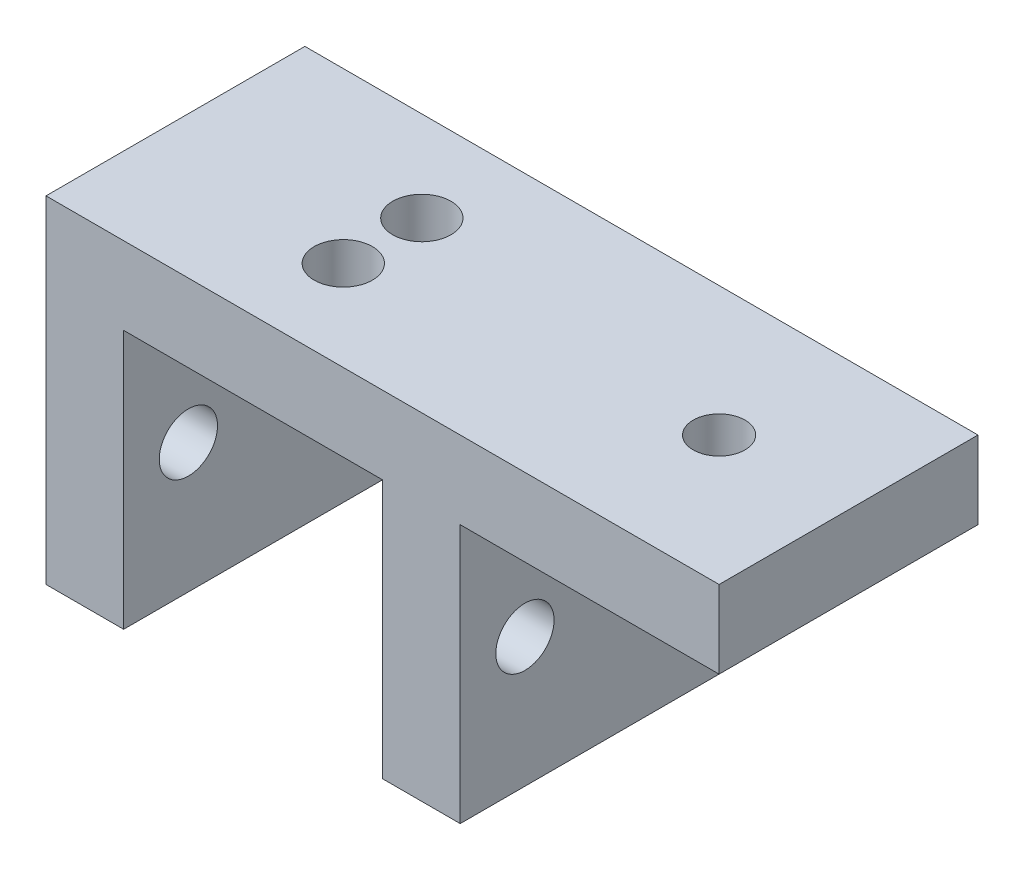
SolidWorks part; units mm, degrees
ref_plane "Front Plane" through (0, 0, 0) normal (0, 0, 1) x (1, 0, 0)
ref_plane "Top Plane" through (0, 0, 0) normal (0, 1, 0) x (1, 0, 0)
ref_plane "Right Plane" through (0, 0, 0) normal (1, 0, 0) x (0, 0, -1)
sketch "Sketch7" plane through (0, 0, 0) normal (0, 0, 1) x (1, 0, 0)
  line L0 (-52, -26) -> (-52, 0)
  line L2 (-20, -6) -> (-20, -26)
  line L3 (-20, -26) -> (-26, -26)
  line L4 (-26, -26) -> (-26, -6)
  line L5 (-26, -6) -> (-46, -6)
  line L6 (-46, -6) -> (-46, -26)
  line L7 (-46, -26) -> (-52, -26)
  line L8 (-20, -6) -> (0, -6)
  line L9 (0, -6) -> (0, 0)
  line L10 (-52, 0) -> (0, 0)
  point P3 (0, 0)
  dimension "D1" = 20
  dimension "D2" = 6
  dimension "D3" = 6
  dimension "D4" = 20
  dimension "D5" = 6
  dimension "D6" = 20
extrude "Boss-Extrude3" add sketch "Sketch7" along normal blind 20
sketch "Sketch9" plane through (-46, 0, 0) normal (1, 0, 0) x (0, 0, -1)
  line L0 (-15, -16) -> (-20, -16) construction
  line L1 (-20, -26) -> (-20, -6) construction
  line L2 (-10, -6) -> (-10, -26) construction
  line L3 (-20, -6) -> (0, -6) construction
  line L4 (-20, -26) -> (0, -26) construction
  line L5 (-15, -16) -> (-10, -16) construction
  circle A0 centre (-15, -16) radius 2.25
  circle A1 centre (-5, -16) radius 2.25
  dimension "D1" = 4.5
extrude "Cut-Extrude1" cut sketch "Sketch9" against normal through all both and the other way through all
sketch "Sketch10" plane through (0, -6, 0) normal (0, -1, 0) x (1, 0, 0)
  line L0 (-46, 10) -> (-26, 10) construction
  line L1 (-46, 20) -> (-46, 0) construction
  line L2 (-26, 20) -> (-26, 0) construction
  line L3 (-36, 10) -> (-36, 6.9662) construction
  line L4 (-36, 6.9662) -> (-36, 0) construction
  line L5 (-46, 0) -> (-26, 0) construction
  circle A0 centre (-36, 6.9662) radius 2.25
  circle A1 centre (-36, 13.0338) radius 2.25
  dimension "D1" = 4.5
extrude "Cut-Extrude2" cut sketch "Sketch10" against normal through all both
sketch "Sketch11" plane through (0, -6, 0) normal (0, -1, 0) x (1, 0, 0)
  line L0 (-20, 20) -> (0, 0) construction
  circle A0 centre (-10, 10) radius 2
  dimension "D1" = 4
extrude "Cut-Extrude3" cut sketch "Sketch11" against normal through all both
